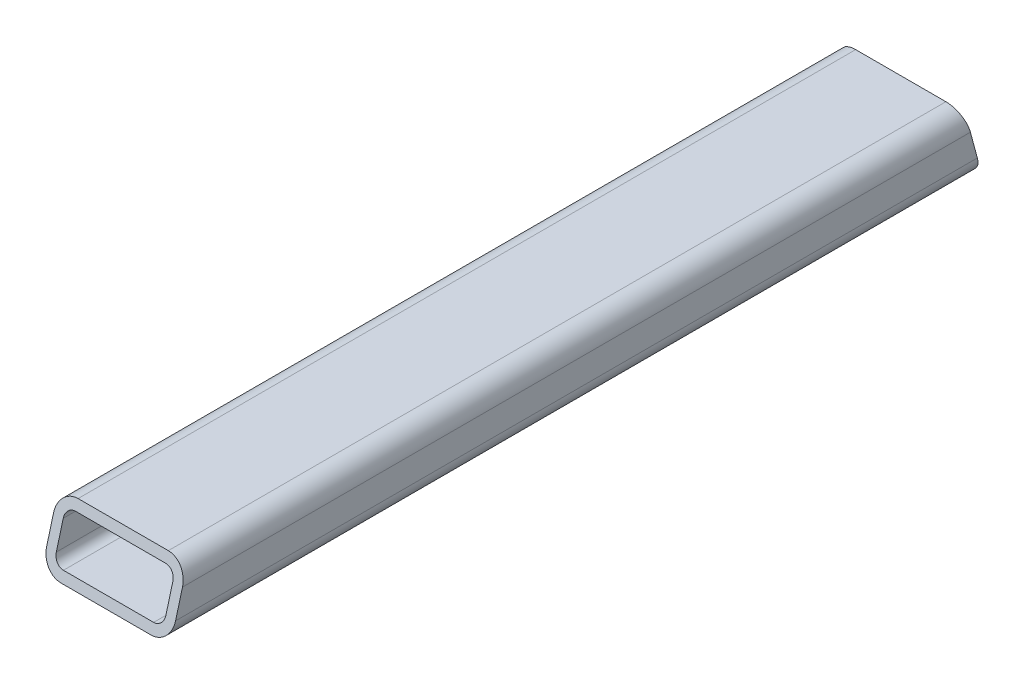
SolidWorks part; units mm, degrees
material "Ст 3 ГОСТ 380-88"
ref_plane "Спереди" through (0, 0, 0) normal (0, 0, 1) x (1, 0, 0)
ref_plane "Сверху" through (0, 0, 0) normal (0, 1, 0) x (1, 0, 0)
ref_plane "Справа" through (0, 0, 0) normal (1, 0, 0) x (0, 0, -1)
sketch "Эскиз1" plane through (0, 0, 0) normal (0, 0, 1) x (1, 0, 0)
  line L1 (-14, 10) -> (14, 10)
  line L2 (-20, 4) -> (-20, -4)
  line L3 (-14, -10) -> (14, -10)
  line L4 (20, 4) -> (20, -4)
  line L5 (-20, 10) -> (20, -10) construction
  line L6 (-20, -10) -> (20, 10) construction
  arc A0 (14, -10) -> (20, -4) centre (14, -4) ccw
  arc A1 (-14, 10) -> (-20, 4) centre (-14, 4) ccw
  arc A2 (-20, -4) -> (-14, -10) centre (-14, -4) ccw
  arc A3 (14, 10) -> (20, 4) centre (14, 4) cw
  point P0 (0, 0)
  dimension "D3" = 6
  dimension "D4" = 6
  dimension "D1" = 20
  dimension "D2" = 40
extrude "Бобышка-Вытянуть1" add sketch "Эскиз1" along normal blind 126 and the other way blind 126
shell "Оболочка1" thickness 3 removed face at (0, 0, -126) removed face at (0, 0, 126)
chamfer "Фаска1" distance 20 angle 15 2 edges at (0, 10, -126) (0, 10, 126) tangent propagation no first distance on face at (0, 0, -126) first distance on face at (0, 0, 126)
